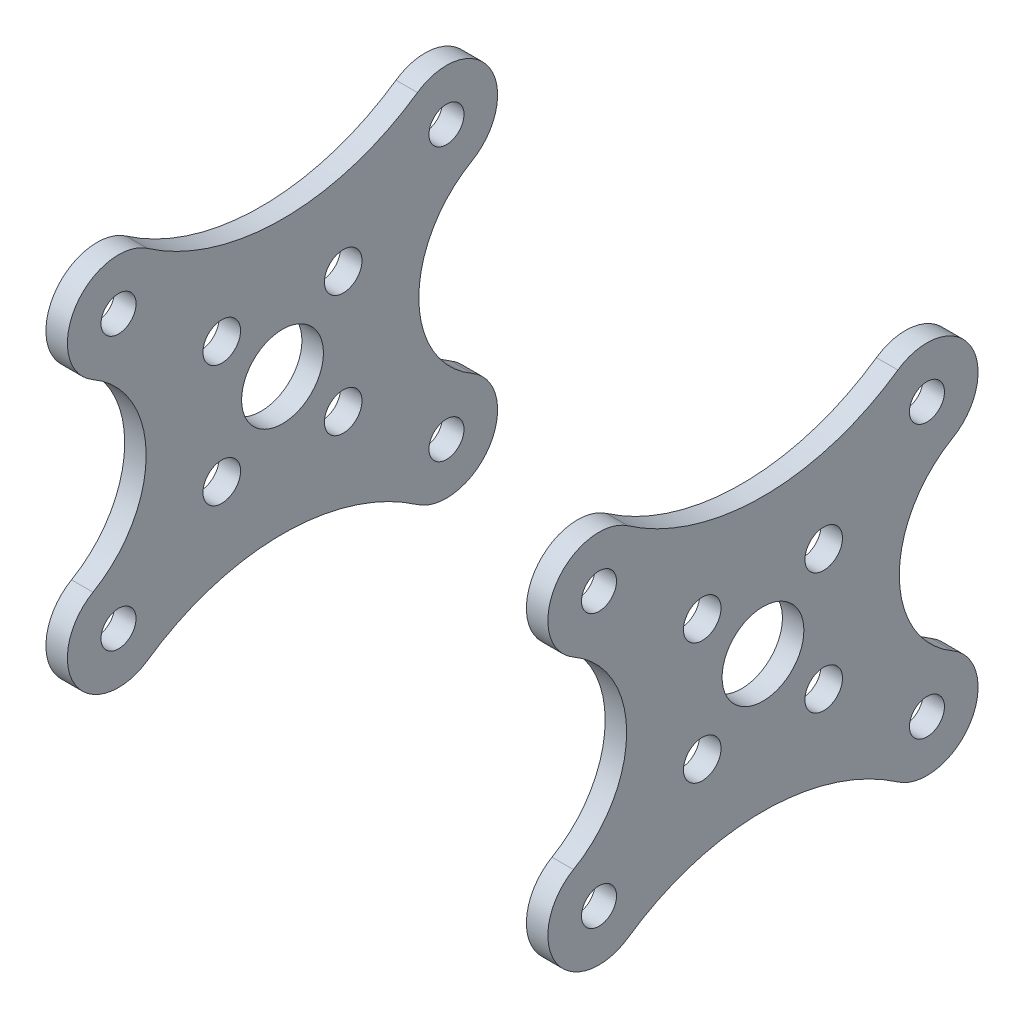
SolidWorks part; units mm, degrees
material "TPU"
ref_plane "Front Plane" through (0, 0, 0) normal (0, 0, 1) x (1, 0, 0)
ref_plane "Top Plane" through (0, 0, 0) normal (0, 1, 0) x (1, 0, 0)
ref_plane "Right Plane" through (0, 0, 0) normal (1, 0, 0) x (0, 0, -1)
ref_plane "Plane2" through (23.38, 0, 0) normal (1, 0, 0) x (0, 0, -1)
sketch "Sketch1" plane through (23.38, 0, 0) normal (1, 0, 0) x (0, 0, -1)
  line L0 (-18.2721, 15.875) -> (-97.3447, 15.875) construction
  circle A0 centre (-40.279, 12.7) radius 3.175 construction
  circle A1 centre (-9.7272, 12.7) radius 3.175 construction
  circle A2 centre (-9.7272, -12.7) radius 3.175 construction
  circle A3 centre (-40.279, -12.7) radius 3.175 construction
  circle A4 centre (-40.279, 12.7) radius 4.3656 construction
  circle A5 centre (-9.7272, 12.7) radius 4.3656 construction
  circle A6 centre (-9.7272, -12.7) radius 4.3656 construction
  circle A7 centre (-40.279, -12.7) radius 4.3656 construction
  circle A8 centre (-40.279, 12.7) radius 1.4224 construction
  circle A9 centre (-25.0031, 0) radius 12.7 construction
  arc A10 (-12.4337, 16.6187) -> (-7.3489, 8.5739) centre (-9.7272, 12.7) cw
  arc A11 (-7.3489, -8.5739) -> (-12.4337, -16.6187) centre (-9.7272, -12.7) cw
  arc A12 (-37.5725, -16.6187) -> (-42.6573, -8.5739) centre (-40.279, -12.7) cw
  arc A13 (-42.6573, 8.5739) -> (-37.5725, 16.6187) centre (-40.279, 12.7) cw
  circle A14 centre (-25.0031, 0) radius 15.5 construction
  arc A15 (-42.6573, 8.5739) -> (-42.6573, -8.5739) centre (-47.5993, 0) cw
  arc A16 (-7.3489, -8.5739) -> (-7.3489, 8.5739) centre (-2.407, 0) cw
  arc A17 (-37.5725, 16.6187) -> (-12.4337, 16.6187) centre (-25.0031, 34.8178) ccw
  arc A18 (-37.5725, -16.6187) -> (-12.4337, -16.6187) centre (-25.0031, -34.8178) cw
  circle A21 centre (-25.0031, 0) radius 15.5 construction
  dimension "D1" = 6.35
  dimension "D2" = 1.1906
  dimension "D3" = 2.8448
  dimension "D4" = 1.5875
  dimension "D5" = 25.4
extrude "Boss-Extrude1" add sketch "Sketch1" against normal blind 2
sketch "Sketch2" plane through (21.38, 0, 0) normal (-1, 0, 0) x (0, 0, 1)
  line L0 (47.5993, 0) -> (2.407, 0) construction
  line L3 (25.0031, 12.7) -> (25.0031, -12.7) construction
  line L7 (19.3463, -5.6569) -> (30.66, 5.6569) construction
  line L8 (19.3463, 5.6569) -> (30.66, -5.6569) construction
  circle A1 centre (19.3463, 5.6569) radius 1.75
  circle A2 centre (19.3463, -5.6569) radius 1.75
  circle A3 centre (30.66, -5.6569) radius 1.75
  circle A4 centre (30.66, 5.6569) radius 1.75
  arc A5 (42.6573, 8.5739) -> (42.6573, -8.5739) centre (47.5993, 0) ccw construction
  arc A6 (7.3489, -8.5739) -> (7.3489, 8.5739) centre (2.407, 0) ccw construction
  arc A7 (12.4337, 16.6187) -> (37.5725, 16.6187) centre (25.0031, 34.8178) ccw construction
  circle A8 centre (25.0031, 0) radius 3.81
  point P16 (25.0031, 0)
  dimension "D4" = 3.5
  dimension "D5" = 7.62
  dimension "D1" = 16
  dimension "D2" = 16
  dimension "D3" = 45
extrude "Cut-Extrude1" cut sketch "Sketch2" against normal up to surface (2 mm away) up to face at (23.38, 0, 25.0031)
sketch "Sketch4" [suppressed] plane through (25.92, 0, 0) normal (1, 0, 0) x (0, 0, -1)
  circle A0 centre (-14.4897, 12.7) radius 4.7625
  circle A1 centre (-45.0415, 12.7) radius 4.7625
  circle A2 centre (-45.0415, -12.7) radius 4.7625
  circle A3 centre (-14.4897, -12.7) radius 4.7625
  arc A4 (-15.6935, -17.3078) -> (-10.8058, -9.6817) centre (-14.4897, -12.7) ccw construction
  arc A5 (-10.8058, 9.6817) -> (-15.6935, 17.3078) centre (-14.4897, 12.7) ccw construction
  arc A6 (-43.8377, 17.3078) -> (-48.7254, 9.6817) centre (-45.0415, 12.7) ccw construction
  arc A7 (-48.7254, -9.6817) -> (-43.8377, -17.3078) centre (-45.0415, -12.7) ccw construction
extrude "Boss-Extrude2" [suppressed] add sketch "Sketch4" against normal up to surface (11.43 mm away)
fillet "Fillet1" [suppressed] radius 2.54
hole_wizard "#4 Clearance Hole1" positions "Sketch6" profile "Sketch8" hole size "#4" standard "ANSI Inch" end condition up to next
sketch "Sketch6" plane through (21.38, 0, 0) normal (1, 0, 0) x (0, 0, -1)
  arc A0 (-37.5725, 16.6187) -> (-42.6573, 8.5739) centre (-40.279, 12.7) ccw construction
  arc A1 (-7.3489, 8.5739) -> (-12.4337, 16.6187) centre (-9.7272, 12.7) ccw construction
  arc A2 (-12.4337, -16.6187) -> (-7.3489, -8.5739) centre (-9.7272, -12.7) ccw construction
  arc A3 (-42.6573, -8.5739) -> (-37.5725, -16.6187) centre (-40.279, -12.7) ccw construction
  point P0 (-40.279, 12.7)
  point P3 (-9.7272, 12.7)
  point P6 (-9.7272, -12.7)
  point P9 (-40.279, -12.7)
sketch "Sketch8" plane through (21.38, 12.7, 40.279) normal (0, 1, 0) x (0, 0, 1)
  line L0 (0, 0) -> (0, 2)
  line L1 (0, 2) -> (1.6319, 2)
  line L2 (1.6319, 2) -> (1.6319, 0)
  line L5 (1.6319, 0) -> (0, 0)
  line L11 (0, -6.35) -> (0, 107.95) construction
  dimension "Thru Hole Dia." = 3.2639
  dimension "Thru Hole Depth" = 2
chamfer "Chamfer1" [suppressed] distance 2.032 angle 45
mirror "Mirror1" about plane through (0, 0, 0) normal (1, 0, 0) of bodies 106 104
equation "\"D1@Sketch2\"=16mm"
equation "\"D2@Sketch2\"=16mm"
equation "\"D1@Boss-Extrude1\"=2mm"
